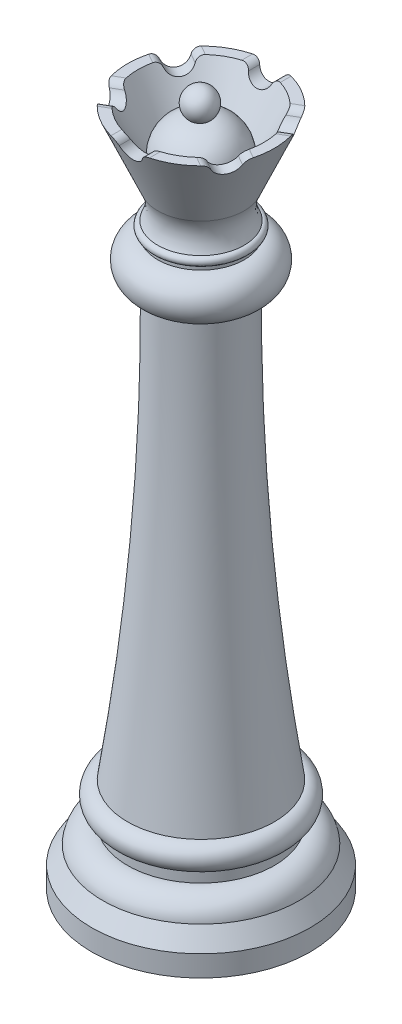
SolidWorks part; units mm, degrees
ref_plane "Front Plane" through (0, 0, 0) normal (0, 0, 1) x (1, 0, 0)
ref_plane "Top Plane" through (0, 0, 0) normal (0, 1, 0) x (1, 0, 0)
ref_plane "Right Plane" through (0, 0, 0) normal (1, 0, 0) x (0, 0, -1)
sketch "Sketch1" plane through (0, 0, 0) normal (0, 0, 1) x (1, 0, 0)
  line L0 (0, 0) -> (6.604, 0)
  line L1 (0, 0) -> (0, 42.2584)
  line L2 (6.604, 0) -> (6.604, 1.27)
  line L3 (6.604, 1.27) -> (5.9351, 2.3496)
  line L4 (4.436, 3.438) -> (4.436, 4.2)
  line L5 (2.6156, 34.2327) -> (2.6156, 34.4867)
  line L16 (2.6076, 36.7939) -> (4.436, 40.9805)
  line L17 (4.436, 40.9805) -> (0, 40.9805)
  arc A0 (5.9351, 2.3496) -> (4.436, 3.438) centre (4.6751, 2.1907) ccw
  arc A1 (4.436, 4.2) -> (4.436, 5.724) centre (4.436, 4.962) ccw
  arc A2 (2.5939, 31.6928) -> (2.6156, 34.2327) centre (2.6048, 32.9627) ccw
  arc A6 (0.5192, 40.9805) -> (0.5174, 40.9906) centre (0.0319, 40.8984) ccw
  arc A13 (2.6156, 34.4867) -> (2.6156, 34.9947) centre (2.6156, 34.7407) ccw
  spline S0 degree 2 poles (4.436, 5.724) (2.4822, 18.6234) (2.5939, 31.6928) knots 0 0 0 1 1 1
  spline S1 degree 2 poles (2.6156, 34.9947) (2.122, 35.9021) (2.6076, 36.7939) knots 0 0 0 1 1 1
  dimension "D6" = 1.27
  dimension "D7" = 0.762
  dimension "D8" = 1.27
  dimension "D10" = 0.254
  dimension "D1" = 6.604
  dimension "D2" = 4.436
  dimension "D3" = 1.27
  dimension "D4" = 1.27
  dimension "D5" = 0.762
  dimension "D9" = 0.254
  dimension "D11" = 4.5685
revolve "Revolve1" add sketch "Sketch1" angle 360 about L1 region at (1.9233, 18.1361, 0)
sketch "Sketch2" plane through (0, 40.9805, 0) normal (0, 1, 0) x (1, 0, 0)
  circle A1 centre (0, 0) radius 3.81
  dimension "D1" = 7.62
extrude "Cut-Extrude4" cut sketch "Sketch2" against normal blind 2.54 draft 30
sketch "Sketch4" plane through (0, 0, 0) normal (0, 0, 1) x (1, 0, 0)
  line L0 (0, 40.9805) -> (0, 40.2185) construction
  line L1 (4.436, 40.9805) -> (-4.436, 40.9805) construction
  circle A1 centre (0, 40.9805) radius 0.762
  dimension "D2" = 1.524
  dimension "D1" = 0.762
extrude "Cut-Extrude5" cut sketch "Sketch4" against normal blind 6.096 contours A1
pattern_circular "CirPattern1" count 6 every 60 about axis through (0, 40.9805, 0) along (0, 1, 0) of "Cut-Extrude5"
sketch "Sketch5" plane through (0, 38.4405, 0) normal (0, 1, 0) x (1, 0, 0)
  circle A0 centre (0, 0) radius 2.3435
extrude "Boss-Extrude1" add sketch "Sketch5" along normal blind 2.032
fillet "Fillet7" radius 2.032 1 edges at (0, 40.4725, 2.3435) type face fillet first side face at (0, 40.4725, 2.3435) second side face at (0, 40.4725, 2.3435)
sketch "Sketch6" plane through (0, 0, 0) normal (0, 0, 1) x (1, 0, 0)
  line L0 (-0.0652, 40.4725) -> (-0.0652, 41.7425) construction
  line L1 (0.3115, 40.4725) -> (-0.3115, 40.4725) construction
  line L2 (-0.0652, 41.7425) -> (-0.0652, 41.9965) construction
  line L3 (-0.0652, 41.9965) -> (-0.0652, 40.2185) construction
  line L4 (-0.0652, 41.9965) -> (-0.0652, 40.2185)
  arc A0 (-0.0652, 41.9965) -> (-0.0652, 40.2185) centre (-0.0652, 41.1075) ccw
  dimension "D2" = 1.778
  dimension "D1" = 1.27
revolve "Revolve2" add sketch "Sketch6" angle 360 about L4
fillet "Fillet8" radius 0.508 12 edges at (-3.1277, 40.9805, 2.6857) (-3.8897, 40.9805, 1.3659) (0.762, 40.9805, 4.0515) (-0.762, 40.9805, 4.0515) (3.8897, 40.9805, 1.3659) (3.1277, 40.9805, 2.6857) (3.1277, 40.9805, -2.6857) (3.8897, 40.9805, -1.3659) (0.762, 40.9805, -4.0515) (-0.762, 40.9805, -4.0515) (-3.8897, 40.9805, -1.3659) (-3.1277, 40.9805, -2.6857)
